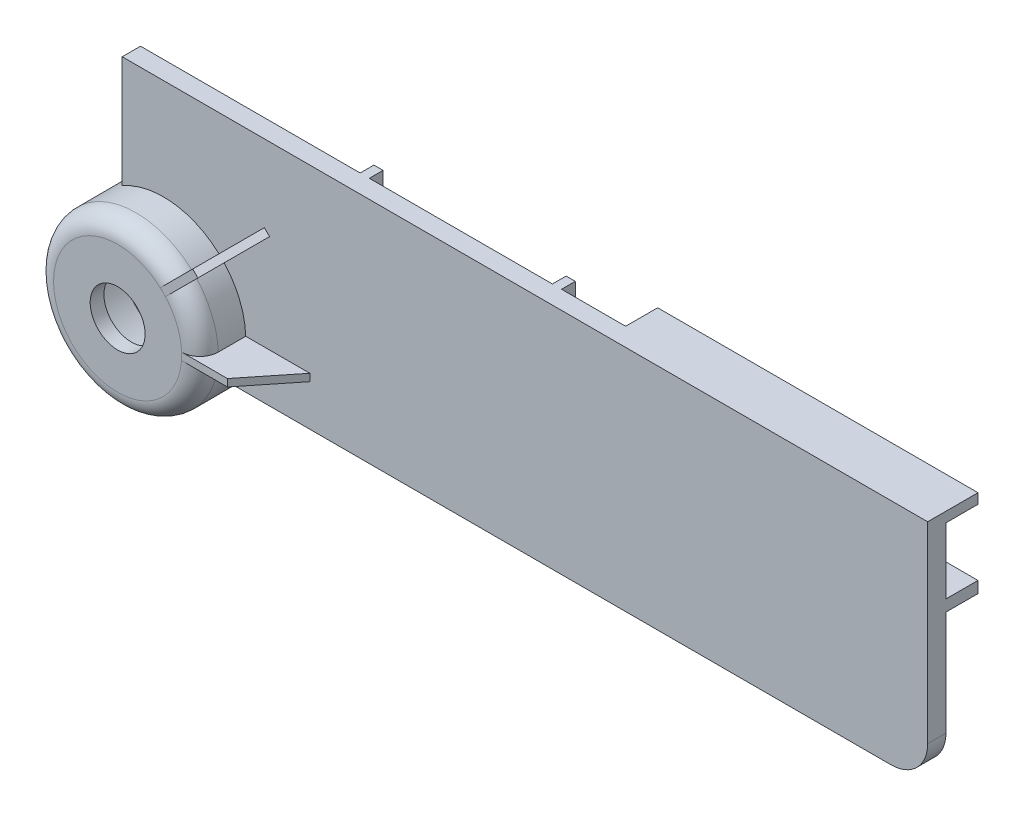
SolidWorks part; units mm, degrees
ref_plane "Piano frontale" through (0, 0, 0) normal (0, 0, 1) x (1, 0, 0)
ref_plane "Piano superiore" through (0, 0, 0) normal (0, 1, 0) x (1, 0, 0)
ref_plane "Piano destro" through (0, 0, 0) normal (1, 0, 0) x (0, 0, -1)
sketch "Schizzo1" plane through (0, 0, 0) normal (0, 0, 1) x (1, 0, 0)
  line L1 (-44, -12.5) -> (44, -12.5)
  line L2 (-44, -12.5) -> (-44, 12.5)
  line L3 (-44, 12.5) -> (44, 12.5)
  line L4 (44, -12.5) -> (44, 12.5)
  line L5 (-44, -12.5) -> (44, 12.5) construction
  line L6 (-44, 12.5) -> (44, -12.5) construction
  point P0 (0, 0)
  dimension "D1" = 25
  dimension "D2" = 88
extrude "Estrusione-Estrusione1" add sketch "Schizzo1" along normal blind 2
sketch "Schizzo2" plane through (0, 0, 0) normal (0, 0, 1) x (1, 0, 0)
  line L0 (44, 12.5) -> (9, 12.5)
  line L1 (44, 12.5) -> (-44, 12.5) construction
  line L2 (9, 12.5) -> (9, 11.4)
  line L3 (9, 11.4) -> (44, 11.4)
  line L4 (44, -12.5) -> (44, 12.5) construction
  line L5 (44, 11.4) -> (44, 12.5)
  dimension "D1" = 35
  dimension "D2" = 1.1
extrude "Estrusione-Estrusione2" add sketch "Schizzo2" against normal blind 3.5
sketch "Schizzo3" plane through (0, 0, 0) normal (0, 0, 1) x (1, 0, 0)
  line L0 (44, 4.2) -> (-44, 4.2)
  line L1 (44, -12.5) -> (44, 11.4) construction
  line L2 (-44, 12.5) -> (-44, -12.5) construction
  line L3 (-44, 4.2) -> (-44, 2.95)
  line L4 (-44, 2.95) -> (44, 2.95)
  line L5 (44, 2.95) -> (44, 4.2)
  line L6 (9, 11.4) -> (44, 11.4) construction
  dimension "D1" = 1.25
  dimension "D2" = 7.2
extrude "Estrusione-Estrusione3" add sketch "Schizzo3" against normal blind 3.5
sketch "Schizzo4" plane through (0, 0, 0) normal (0, 0, 1) x (1, 0, 0)
  line L0 (36.5, -5.7424) -> (-30, -5.7424)
  line L1 (-30, -5.7424) -> (-30, -6.9924)
  line L2 (-30, -6.9924) -> (36.5, -6.9924)
  line L3 (36.5, -6.9924) -> (36.5, -5.7424)
  line L4 (-44, 2.95) -> (44, 2.95) construction
  line L5 (-44, 2.95) -> (-44, -12.5) construction
  point P2 (-30, -6.3674)
  dimension "D1" = 66.5
  dimension "D2" = 1.25
  dimension "D3" = 8.6924
  dimension "D4" = 14
extrude "Estrusione-Estrusione4" add sketch "Schizzo4" against normal blind 3.5
sketch "Schizzo5" plane through (0, -6.9924, 0) normal (0, -1, 0) x (1, 0, 0)
  line L0 (36.5, -3.5) -> (39.5, 0)
  line L1 (39.5, 0) -> (36.5, 0)
  line L2 (36.5, 0) -> (36.5, -3.5)
  dimension "D1" = 3
extrude "Estrusione-Estrusione5" add sketch "Schizzo5" against normal blind 1.25
sketch "Schizzo6" plane through (0, 0, 0) normal (0, 0, 1) x (1, 0, 0)
  line L0 (-19, 12.5) -> (-20, 12.5)
  line L1 (9, 12.5) -> (-44, 12.5) construction
  line L2 (-20, 12.5) -> (-20, -12.5)
  line L3 (-44, -12.5) -> (44, -12.5) construction
  line L4 (-20, -12.5) -> (-19, -12.5)
  line L5 (-19, -12.5) -> (-19, 12.5)
  line L6 (-44, 12.5) -> (-44, 4.2) construction
  dimension "D1" = 24
  dimension "D2" = 1
  dimension "D3" = 25
extrude "Estrusione-Estrusione7" add sketch "Schizzo6" against normal blind 1.5
sketch "Schizzo7" plane through (0, 0, 0) normal (0, 0, 1) x (1, 0, 0)
  line L0 (1, 12.5) -> (1, -12.5)
  line L1 (9, 12.5) -> (-19, 12.5) construction
  line L2 (-19, -12.5) -> (44, -12.5) construction
  line L3 (1, -12.5) -> (2, -12.5)
  line L4 (2, -12.5) -> (2, 12.5)
  line L5 (2, 12.5) -> (1, 12.5)
  line L6 (-19, 4.2) -> (-19, 12.5) construction
  dimension "D1" = 20
  dimension "D2" = 1
extrude "Estrusione-Estrusione8" add sketch "Schizzo7" against normal blind 1.5
sketch "Schizzo8" plane through (0, 0, 0) normal (0, 0, 1) x (1, 0, 0)
  line L0 (22, 11.4) -> (22, -12.5)
  line L1 (9, 11.4) -> (44, 11.4) construction
  line L2 (2, -12.5) -> (44, -12.5) construction
  line L3 (22, -12.5) -> (23, -12.5)
  line L4 (23, -12.5) -> (23, 11.4)
  line L5 (23, 11.4) -> (22, 11.4)
  line L6 (2, 4.2) -> (2, 12.5) construction
  dimension "D1" = 20
  dimension "D2" = 1
extrude "Estrusione-Estrusione9" add sketch "Schizzo8" against normal blind 1.5
fillet "Raccordo2" radius 4 1 edges at (44, -12.5, 1) type face fillet first side face at (44, 3.71, -1) second side face at (1.125, -12.5, -0.3125)
sketch "Schizzo9" plane through (0, 0, 0) normal (0, 0, 1) x (1, 0, 0)
  line L0 (-44, 12.5) -> (-44, -12.5) construction
  line L1 (44, 12.5) -> (-44, 12.5) construction
  circle A0 centre (-39.5, -7.5) radius 9
  dimension "D1" = 18
  dimension "D2" = 4.5
  dimension "D3" = 20
extrude "Estrusione-Sottile1" add sketch "Schizzo9" along normal blind 7 thin thin type one direction reverse wall 2
sketch "Schizzo10" plane through (0, 0, 2) normal (0, 0, 1) x (1, 0, 0)
  line L2 (-44, -12.5) -> (-34.601, -12.5)
  line L3 (-44, -2.1381) -> (-44, -12.5)
  line L4 (-44, -12.5) -> (-34.601, -12.5)
  line L5 (-44, -2.1381) -> (-44, -12.5)
  arc A1 (-34.601, -12.5) -> (-44, -2.1381) centre (-39.5, -7.5) ccw
  arc A2 (-34.601, -12.5) -> (-44, -2.1381) centre (-39.5, -7.5) ccw
  dimension "D1" = 0
extrude "Taglio-Estrusione1" cut sketch "Schizzo10" against normal mid plane 7
sketch "Schizzo11" plane through (0, 0, 0) normal (0, 0, 1) x (1, 0, 0)
  circle A0 centre (-39.5, -7.5) radius 7
  circle A2 centre (-39.5, -7.5) radius 7 construction
extrude "Estrusione-Sottile2" add sketch "Schizzo11" against normal blind 1.5 from offset 7 thin thin type one direction reverse wall 4
fillet "Raccordo4" radius 2 1 edges at (-30.5, -7.5, 7)
sketch "Schizzo12" plane through (0, 0, 2) normal (0, 0, 1) x (1, 0, 0)
  line L0 (-27.4945, -7.2) -> (-32.495, -7.2)
  line L1 (-27.4945, -7.2) -> (-27.5059, -8)
  line L2 (-27.5059, -8) -> (-32.5064, -8)
  line L3 (-32.5064, -8) -> (-32.495, -7.2)
  line L4 (-32.0167, -12.5) -> (40, -12.5) construction
  circle A0 centre (-39.5, -7.5) radius 7 construction
  circle A1 centre (-39.5, -7.5) radius 7 construction
  point P9 (-32.5007, -7.6)
  dimension "D1" = 4.5
  dimension "D2" = 0.8
  dimension "D3" = 5
extrude "Estrusione-Estrusione10" add sketch "Schizzo12" along normal blind 5
sketch "Schizzo14" plane through (0, -8, 0) normal (0, -1, 0) x (1, 0, 0)
  line L0 (-27.5059, 2) -> (-23.5059, 2)
  line L1 (-23.5059, 2) -> (-27.5059, 7)
  line L2 (-27.5059, 7) -> (-27.5059, 2)
  dimension "D1" = 4
extrude "Estrusione-Estrusione11" add sketch "Schizzo14" against normal blind 0.8
sketch "Schizzo16" plane through (0, 0, 2) normal (0, 0, 1) x (1, 0, 0)
  line L0 (-30.7319, 0.7024) -> (-34.2674, -2.8331)
  line L1 (-30.7319, 0.7024) -> (-31.2976, 1.2681)
  line L2 (-31.2976, 1.2681) -> (-34.8331, -2.2674)
  line L3 (-34.8331, -2.2674) -> (-34.2674, -2.8331)
  line L4 (-23.5059, -7.2) -> (-30.505, -7.2) construction
  line L5 (-39.5, -7.5) -> (-19.5, 12.5) construction
  line L6 (44, 12.5) -> (-44, 12.5) construction
  circle A1 centre (-39.5, -7.5) radius 7 construction
  dimension "D1" = 5
  dimension "D2" = 0.8
  dimension "D4" = 45
extrude "Estrusione-Estrusione12" add sketch "Schizzo16" along normal blind 5
sketch "Schizzo17" plane through (-15.7172, 15.7172, 0) normal (0.7071, -0.7071, 0) x (0, 0, -1)
  line L0 (-7, -21.234) -> (-2, -17.234)
  line L1 (-2, -17.234) -> (-2, -21.234)
  line L2 (-2, -21.234) -> (-7, -21.234)
  dimension "D1" = 4
extrude "Estrusione-Estrusione13" add sketch "Schizzo17" against normal blind 0.8
